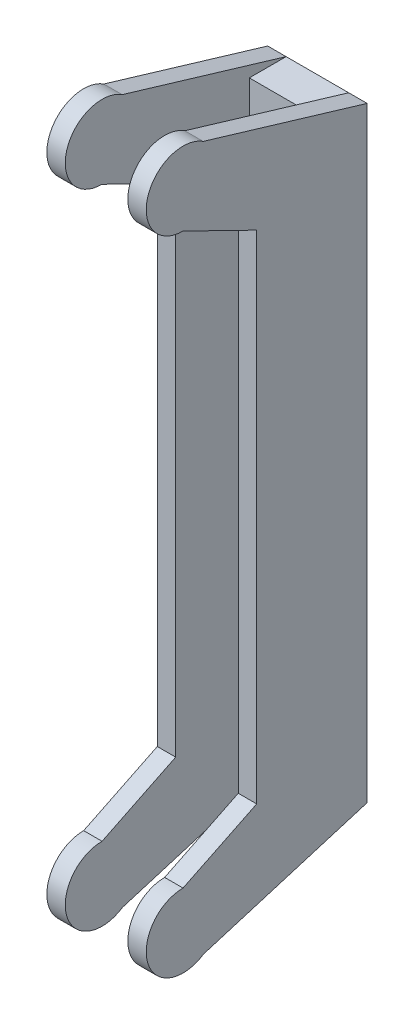
SolidWorks part; units mm, degrees
ref_plane "Alzado" through (0, 0, 0) normal (0, 0, 1) x (1, 0, 0)
ref_plane "Planta" through (0, 0, 0) normal (0, 1, 0) x (1, 0, 0)
ref_plane "Vista lateral" through (0, 0, 0) normal (1, 0, 0) x (0, 0, -1)
sketch "Croquis1" plane through (0, 0, 0) normal (1, 0, 0) x (0, 0, -1)
  line L0 (-29.5065, 95.5696) -> (15, 82.25)
  line L2 (-15, 67.4331) -> (-15, -67.5398)
  line L4 (15, 82.25) -> (15, -82.25)
  line L5 (-15, 82.25) -> (15, -82.25) construction
  line L6 (-15, -82.25) -> (15, 82.25) construction
  line L7 (-29.4721, -95.6595) -> (15, -82.25)
  line L8 (-35, 77.2137) -> (-15, 67.4331)
  line L9 (-35, -77.3263) -> (-15, -67.5398)
  arc A0 (-29.5065, 95.5696) -> (-35, 77.2137) centre (-35, 87.2137) ccw
  arc A1 (-35, -77.3263) -> (-29.4721, -95.6595) centre (-35, -87.3263) ccw
  point P0 (0, 0)
  point P7 (0, 0)
  point P10 (0, 0)
  point P11 (0, 0)
  point P17 (0, 0)
  dimension "D3" = 20
  dimension "D4" = 20
  dimension "D1" = 164.5
  dimension "D2" = 30
  dimension "D5" = 50
  dimension "D6" = 50
  dimension "D7" = 35
  dimension "D8" = 63.94
  dimension "D9" = 174.54
  dimension "D10" = 63.926
  dimension "D11" = 15
extrude "Saliente-Extruir1" add sketch "Croquis1" along normal blind 5
ref_plane "Plano1" through (-8.5, 0, 0) normal (1, 0, 0) x (0, 0, -1)
mirror "Simetría3" about plane through (-8.5, 0, 0) normal (1, 0, 0) of bodies 101
sketch "Croquis3" plane through (-8.5, 0, 0) normal (1, 0, 0) x (0, 0, -1)
  line L1 (5, -82.25) -> (15, -82.25)
  line L2 (5, -82.25) -> (5, 82.25)
  line L3 (5, 82.25) -> (15, 82.25)
  line L4 (15, -82.25) -> (15, 82.25)
  line L5 (5, -82.25) -> (15, 82.25) construction
  line L6 (5, 82.25) -> (15, -82.25) construction
  point P0 (10, 0)
  dimension "D1" = 10
extrude "Saliente-Extruir2" add sketch "Croquis3" along normal mid plane 20
shell "Vaciado1" thickness 8 removed face at (-8.5, 0, -5)
